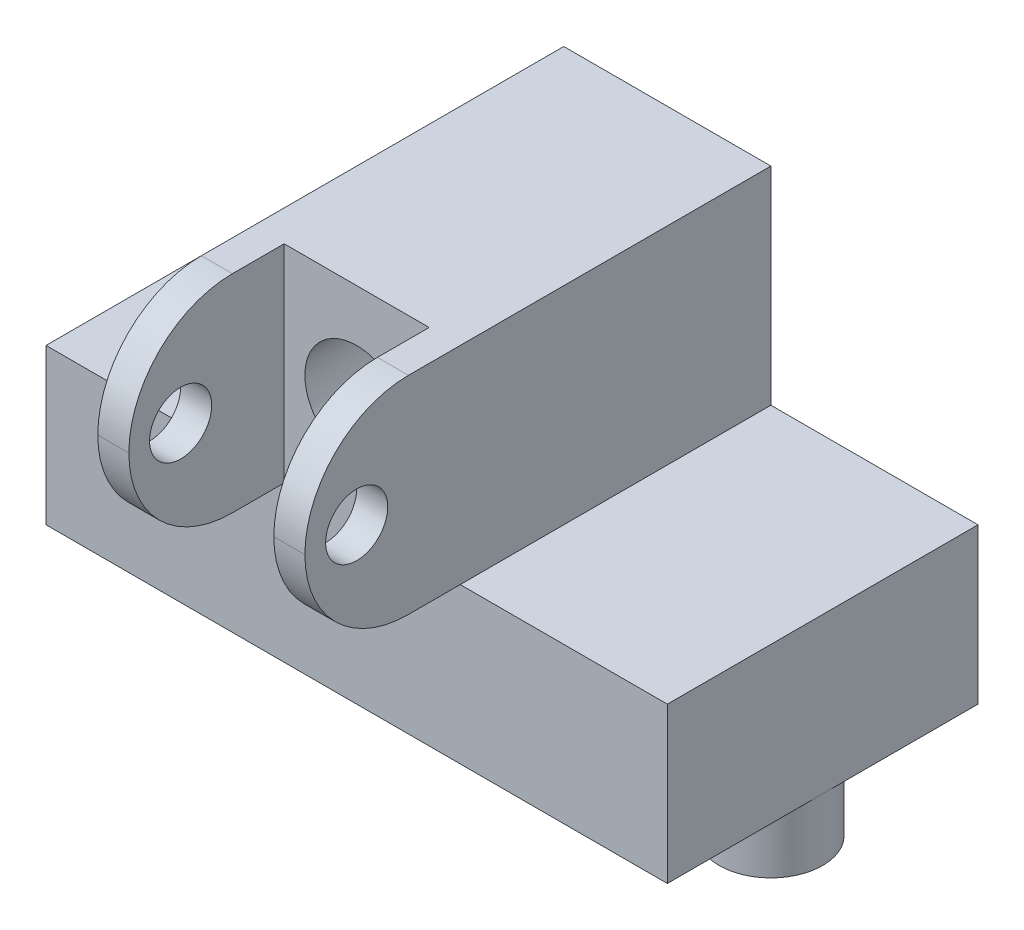
SolidWorks part; units mm, degrees
ref_plane "Plan de face" through (0, 0, 0) normal (0, 0, 1) x (1, 0, 0)
ref_plane "Plan de dessus" through (0, 0, 0) normal (0, 1, 0) x (1, 0, 0)
ref_plane "Plan de droite" through (0, 0, 0) normal (1, 0, 0) x (0, 0, -1)
sketch "Esquisse2" plane through (0, 0, 0) normal (0, 1, 0) x (1, 0, 0)
  line L1 (25, -15) -> (-35, -15)
  line L2 (25, -15) -> (25, 15)
  line L3 (25, 15) -> (-35, 15)
  line L4 (-35, -15) -> (-35, 15)
  point P0 (0, 0)
  dimension "D1" = 60
  dimension "D2" = 30
  dimension "D3" = 15
extrude "Boss.-Extru.1" add sketch "Esquisse2" along normal blind 15
sketch "Esquisse3" plane through (0, 0, 0) normal (0, -1, 0) x (1, 0, 0)
  line L0 (0, 0) -> (26.5883, 0) construction
  line L1 (0, 0) -> (-34.2173, 0) construction
  line L2 (0, 0) -> (0, -11.8019) construction
  circle A0 centre (-20, 0) radius 5
  circle A1 centre (20, 0) radius 5
  point P3 (-20, 0)
  dimension "D1" = 20
extrude "Boss.-Extru.2" add sketch "Esquisse3" along normal blind 6
sketch "Esquisse4" plane through (0, 15, 0) normal (0, 1, 0) x (1, 0, 0)
  line L0 (-35, -15) -> (25, -15) construction
  line L1 (25, 15) -> (-35, 15) construction
  line L2 (-5, 15) -> (-15, 15)
  line L3 (-15, 15) -> (-15, -15)
  line L4 (-15, -15) -> (5, -15)
  line L5 (5, -15) -> (5, 15)
  line L6 (5, 15) -> (-5, 15)
  point P0 (-5, -15)
  point P1 (-5, 15)
  dimension "D1" = 10
  dimension "D2" = 10
extrude "Boss.-Extru.3" add sketch "Esquisse4" along normal blind 20
sketch "Esquisse5" plane through (0, 0, -15) normal (0, 0, -1) x (-1, 0, 0)
  line L0 (-5, 35) -> (15, 15) construction
  line L1 (15, 15) -> (-5, 15) construction
  line L2 (-5, 15) -> (15, 35) construction
  circle A0 centre (5, 25) radius 5
  dimension "D1" = 10
extrude "Enlèv. mat.-Extru.1" cut sketch "Esquisse5" against normal blind 30
sketch "Esquisse6" plane through (0, 0, 15) normal (0, 0, 1) x (1, 0, 0)
  line L0 (-15, 15) -> (-12, 15) construction
  line L1 (-12, 15) -> (2, 15) construction
  line L2 (-15, 35) -> (5, 35) construction
  line L3 (-15, 15) -> (-12, 15)
  line L4 (-15, 15) -> (-15, 35)
  line L5 (-15, 35) -> (-12, 35)
  line L6 (-12, 15) -> (-12, 35)
  line L7 (5, 35) -> (5, 15) construction
  line L8 (2, 15) -> (5, 15)
  line L9 (2, 15) -> (2, 35)
  line L10 (2, 35) -> (5, 35)
  line L11 (5, 15) -> (5, 35)
  dimension "D1" = 3
  dimension "D2" = 3
extrude "Boss.-Extru.4" add sketch "Esquisse6" along normal blind 15
fillet "Congé2" radius 10 1 edges at (3.5, 35, 30) type face fillet first side face at (-5.875, 35, 15.9375) second side face at (3.5, 25, 30)
fillet "Congé3" radius 10 1 edges at (3.5, 15, 30) type face fillet first side face at (3.5, 20, 30) second side face at (3.125, 15, 24.375)
fillet "Congé4" radius 10 1 edges at (-13.5, 15, 30) type face fillet first side face at (-13.875, 15, 24.375) second side face at (-13.5, 25, 30)
fillet "Congé5" radius 10 1 edges at (-13.5, 35, 30) type face fillet first side face at (-5.875, 35, 13.4375) second side face at (-13.5, 30, 30)
sketch "Esquisse7" plane through (-15, 0, 0) normal (-1, 0, 0) x (0, 0, 1)
  line L0 (20, 35) -> (20, 15) construction
  line L1 (-15, 35) -> (20, 35) construction
  line L2 (20, 25) -> (30, 25) construction
  arc A0 (30, 25) -> (20, 35) centre (20, 25) ccw construction
  arc A1 (20, 15) -> (30, 25) centre (20, 25) ccw construction
  circle A2 centre (25, 25) radius 3
extrude "Enlèv. mat.-Extru.2" cut sketch "Esquisse7" against normal blind 27
